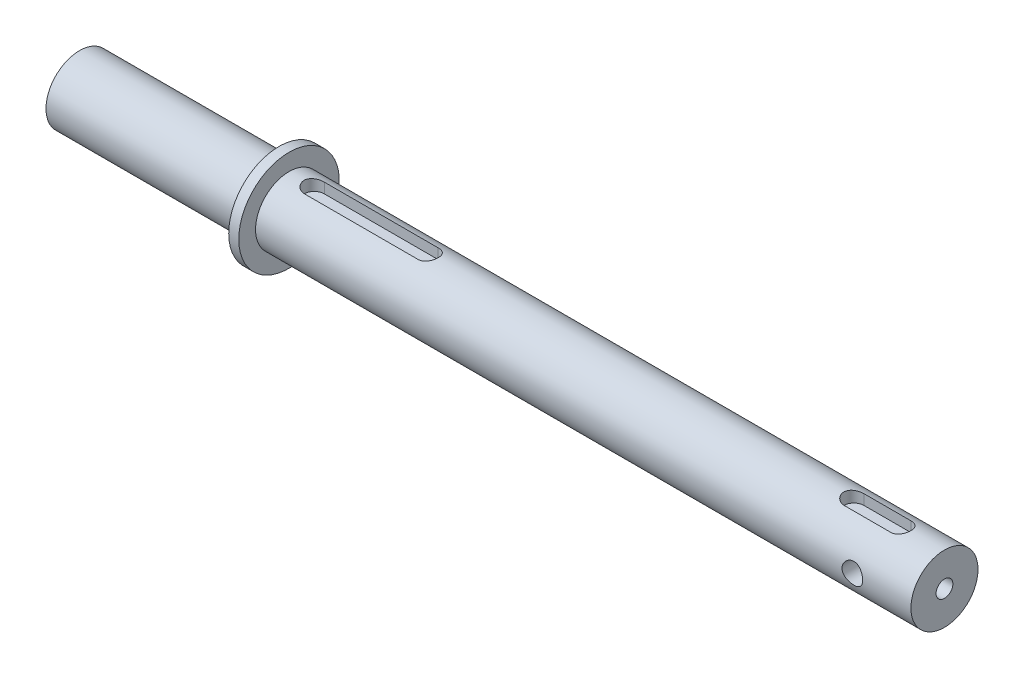
SolidWorks part; units mm, degrees
ref_plane "Alzado" through (0, 0, 0) normal (0, 0, 1) x (1, 0, 0)
ref_plane "Planta" through (0, 0, 0) normal (0, 1, 0) x (1, 0, 0)
ref_plane "Vista lateral" through (0, 0, 0) normal (1, 0, 0) x (0, 0, -1)
sketch "Croquis1" plane through (0, 0, 0) normal (1, 0, 0) x (0, 0, -1)
  circle A0 centre (0, 0) radius 10
  dimension "D1" = 20
extrude "Saliente-Extruir1" add sketch "Croquis1" along normal blind 258 from offset 8
ref_plane "Plano1" through (70.5, 0, 0) normal (-1, 0, 0) x (0, 0, 1)
sketch "Croquis2" plane through (70.5, 0, 0) normal (-1, 0, 0) x (0, 0, 1)
  circle A0 centre (0, 0) radius 15
  dimension "D1" = 30
extrude "Saliente-Extruir2" add sketch "Croquis2" along normal blind 3
sketch "Croquis3" plane through (0, 0, 0) normal (0, 0, 1) x (1, 0, 0)
  circle A0 centre (248.5, 0) radius 3.075
  dimension "D1" = 6.15
extrude "Cortar-Extruir1" cut sketch "Croquis3" against normal up to next and the other way up to next
sketch "Croquis4" plane through (0, 0, 0) normal (0, 1, 0) x (1, 0, 0)
  line L0 (266, 0) -> (231.4531, 0) construction
  line L1 (266, -10) -> (266, 10) construction
  line L2 (239, 0) -> (253, 0) construction
  line L3 (239, 3) -> (253, 3)
  line L4 (239, -3) -> (253, -3)
  arc A0 (239, 3) -> (239, -3) centre (239, 0) ccw
  arc A1 (253, -3) -> (253, 3) centre (253, 0) ccw
  point P7 (246, 0)
  dimension "D1" = 6
  dimension "D2" = 20
  dimension "D3" = 14
extrude "Cortar-Extruir2" cut sketch "Croquis4" against normal blind 3.5 from offset 10
hole_wizard "Taladro roscado M61" positions "Croquis3D2" profile "Croquis7" tap size "M6" standard "DIN"
sketch3d "Croquis3D2"
  circle A0 centre (266, 0, 0) radius 10 construction
  point P0 (266, 0, 0)
  point P5 (276, 0, 0)
sketch "Croquis7" plane through (266, 0, 0) normal (0, 1, 0) x (0, 0, -1)
  line L0 (0, 0) -> (0, 13)
  line L1 (0, 13) -> (2.5, 11.4978)
  line L2 (2.5, 11.4978) -> (2.5, 0)
  line L5 (2.5, 0) -> (0, 0)
  line L10 (0, 13) -> (-2.5, 11.4978) construction
  line L11 (0, -6.35) -> (0, 107.95) construction
  dimension "Diámetro de perforador para roscar" = 5
  dimension "Profundidad de perforador para roscar" = 13
  dimension "Ángulo de perforador" = 118
cosmetic thread "Rosca de taladro1" parameters "D1"=12, "D2"=6
sketch "Croquis8" plane through (0, 0, 0) normal (0, 1, 0) x (1, 0, 0)
  line L0 (8.3, 0) -> (274.8253, 0) construction
  line L1 (8.3, -21) -> (8.3, 21) construction
  line L2 (78, 0) -> (112, 0) construction
  line L3 (78, 3) -> (112, 3)
  line L4 (78, -3) -> (112, -3)
  line L5 (8, 10) -> (8, -10) construction
  arc A0 (78, 3) -> (78, -3) centre (78, 0) ccw
  arc A1 (112, -3) -> (112, 3) centre (112, 0) ccw
  point P7 (95, 0)
  point P14 (75, 0)
  point P15 (115, 0)
  dimension "D1" = 87
  dimension "D2" = 40
  dimension "D3" = 6
extrude "Cortar-Extruir3" cut sketch "Croquis8" against normal blind 3.5 from offset 10
